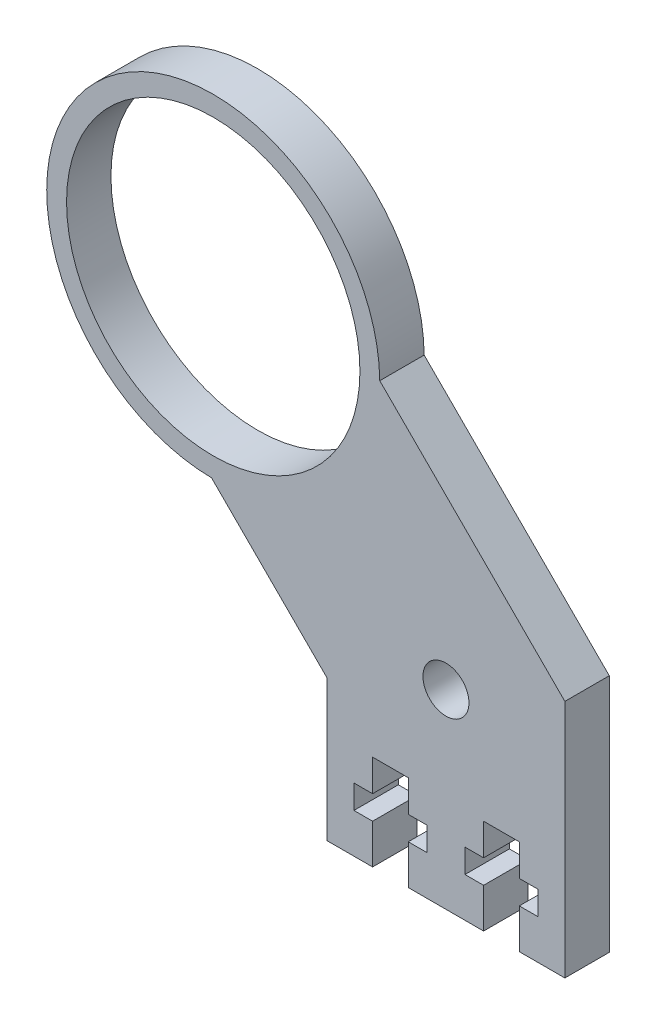
SolidWorks part; units mm, degrees
ref_plane "Front Plane" through (0, 0, 0) normal (0, 0, 1) x (1, 0, 0)
ref_plane "Top Plane" through (0, 0, 0) normal (0, 1, 0) x (1, 0, 0)
ref_plane "Right Plane" through (0, 0, 0) normal (1, 0, 0) x (0, 0, -1)
sketch "Sketch1" plane through (0, 0, 0) normal (0, 0, 1) x (1, 0, 0)
  line L0 (0, 0) -> (-29.3449, 29.3449) construction
  line L1 (0, 0) -> (0, 31.0325) construction
  line L2 (-15, -6.2132) -> (-15, -24)
  line L3 (-15, -24) -> (15, -24)
  line L4 (15, -24) -> (15, 6.2132)
  line L5 (0, 0) -> (0, -24) construction
  line L6 (15, 6.2132) -> (-8.346, 29.5592)
  line L7 (-15, -6.2132) -> (-29.5592, 8.346)
  line L8 (10.6066, 10.6066) -> (-18.7383, 39.9515) construction
  line L9 (-10.6066, -10.6066) -> (-39.9515, 18.7383) construction
  circle A0 centre (0, 0) radius 2.9
  arc A1 (-8.346, 29.5592) -> (-29.5592, 8.346) centre (-29.3449, 29.3449) ccw
  dimension "D1" = 5.8
  dimension "D3" = 42
  dimension "D2" = 41.5
  dimension "D4" = 45
  dimension "D5" = 24
  dimension "D6" = 30
  dimension "D7" = 15
  dimension "D8" = 15
extrude "Boss-Extrude1" add sketch "Sketch1" along normal blind 5.6
sketch "Sketch2" plane through (0, 0, 5.6) normal (0, 0, 1) x (1, 0, 0)
  circle A0 centre (-29.3449, 29.3449) radius 18.5
  dimension "D1" = 37
extrude "Cut-Extrude1" cut sketch "Sketch2" against normal through all
sketch "Sketch3" plane through (0, 0, 5.6) normal (0, 0, 1) x (1, 0, 0)
  line L0 (-15, -24) -> (15, -24) construction
  line L1 (-9.25, -24) -> (-4.75, -24)
  line L2 (-9.25, -24) -> (-9.25, -19)
  line L3 (-9.25, -12) -> (-4.75, -12)
  line L4 (-4.75, -24) -> (-4.75, -19)
  line L5 (0, 0) -> (0, -24) construction
  line L6 (-4.75, -16) -> (-2.4, -16)
  line L7 (-11.6, -16) -> (-9.25, -16)
  line L8 (-11.6, -16) -> (-11.6, -19)
  line L9 (-11.6, -19) -> (-9.25, -19)
  line L10 (-2.4, -16) -> (-2.4, -19)
  line L11 (-9.25, -16) -> (-9.25, -12)
  line L12 (-4.75, -19) -> (-2.4, -19)
  line L13 (-4.75, -16) -> (-4.75, -12)
  line L14 (4.75, -16) -> (4.75, -12)
  line L15 (4.75, -19) -> (2.4, -19)
  line L16 (9.25, -16) -> (9.25, -12)
  line L17 (2.4, -16) -> (2.4, -19)
  line L18 (11.6, -19) -> (9.25, -19)
  line L19 (11.6, -16) -> (11.6, -19)
  line L20 (11.6, -16) -> (9.25, -16)
  line L21 (4.75, -16) -> (2.4, -16)
  line L22 (4.75, -24) -> (4.75, -19)
  line L23 (9.25, -12) -> (4.75, -12)
  line L24 (9.25, -24) -> (9.25, -19)
  line L25 (9.25, -24) -> (4.75, -24)
  point P6 (-7, -12)
  point P18 (-10.425, -19)
  dimension "D1" = 4.5
  dimension "D2" = 7
  dimension "D3" = 12
  dimension "D4" = 9.2
  dimension "D5" = 3
  dimension "D6" = 5
extrude "Cut-Extrude2" cut sketch "Sketch3" against normal through all
equation "\"smallPulleyTeeth\"= 15"
equation "\"largePulleyTeeth\"= 30"
equation "\"eighthThick\"= 2.9mm"
equation "\"sixteenthThick\" = 1.7mm"
equation "\"quarterThick\"=5.6mm"
equation "\"OD\" = 150mm"
equation "\"puckAngle\" = 60.5deg"
equation "\"puckDiam\" = 76.5mm"
equation "\"axlePress\" = 5.8mm"
equation "\"D1@Sketch1\"=\"axlePress\""
equation "\"D1@Boss-Extrude1\"=\"quarterThick\""
equation "\"press\" = 0.2mm"
equation "\"wheelClear\" = 0.3mm"
equation "\"10-32clear\" = 4.5mm"
equation "\"D1@Sketch3\"=\"10-32clear\""
equation "\"6-32clear\" = 3.3mm"
equation "\"8-32clear\" = 4.0mm"
equation "\"wheelHeight\" = 24mm"
equation "\"D5@Sketch1\"=\"wheelHeight\""
